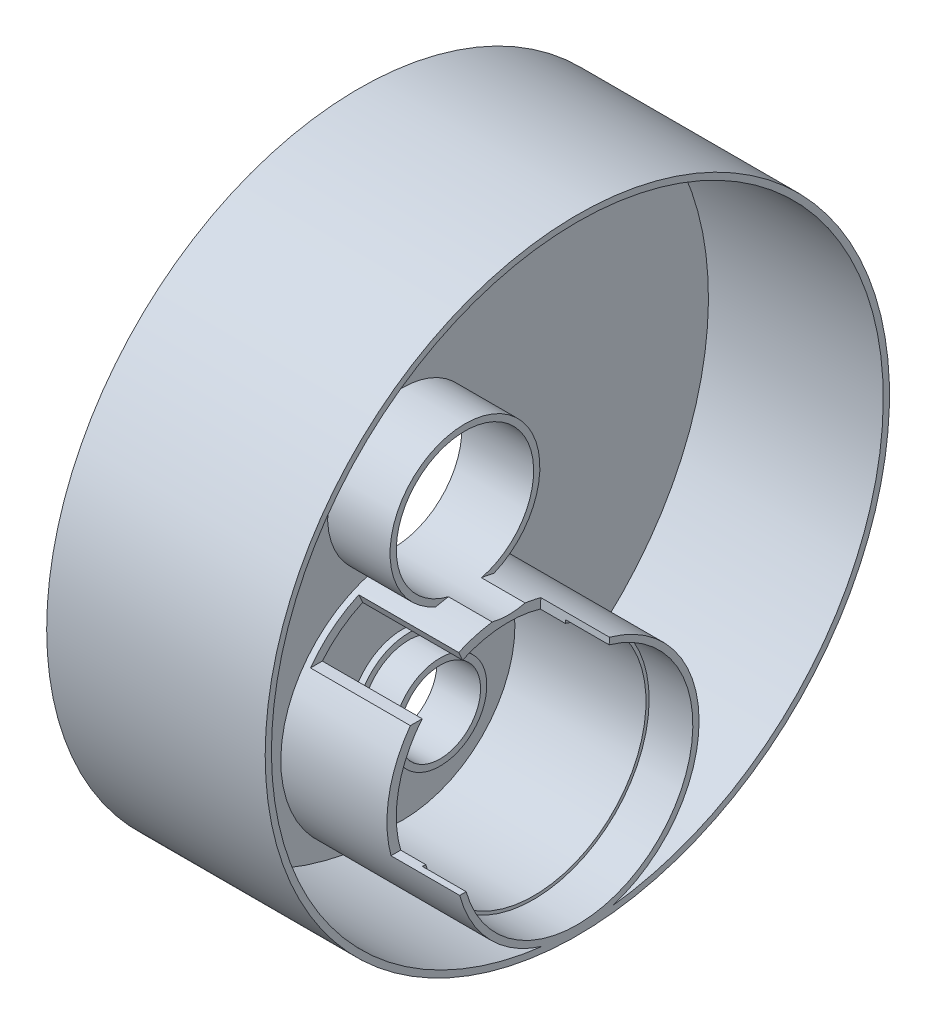
SolidWorks part; units mm, degrees
material "1060 Сплав"
ref_plane "Спереди" through (0, 0, 0) normal (0, 0, 1) x (1, 0, 0)
ref_plane "Сверху" through (0, 0, 0) normal (0, 1, 0) x (1, 0, 0)
ref_plane "Справа" through (0, 0, 0) normal (1, 0, 0) x (0, 0, -1)
sketch "Эскиз1" plane through (0, 0, 0) normal (0, 0, 1) x (1, 0, 0)
  line L0 (0, 0) -> (26039.5549, 0) construction
  line L1 (-27, 7.5) -> (-27, 8.5)
  line L2 (0, 19.5) -> (-29, 19.5)
  line L3 (-29, 19.5) -> (-29, 6.5)
  line L4 (-29, 6.5) -> (-22, 6.5)
  line L5 (-22, 6.5) -> (-22, 7.5)
  line L6 (-22, 7.5) -> (-27, 7.5)
  line L7 (-28, 8.5) -> (-28, 18)
  line L8 (-28, 18) -> (-7, 18)
  line L9 (-7, 18) -> (-7, 18.5)
  line L10 (-7, 18.5) -> (0, 18.5)
  line L11 (0, 18.5) -> (0, 19.5)
  line L12 (-27, 8.5) -> (-28, 8.5)
  dimension "D1" = 18.5
  dimension "D2" = 1
  dimension "D3" = 18
  dimension "D4" = 7
  dimension "D5" = 21
  dimension "D6" = 1
  dimension "D7" = 1
  dimension "D8" = 1
  dimension "D9" = 7.5
  dimension "D10" = 1
  dimension "D11" = 13
  dimension "D12" = 0.5
  dimension "D13" = 5
revolve "Повернуть1" add sketch "Эскиз1" angle 360 about L0
sketch "Эскиз2" plane through (0, 0, 0) normal (1, 0, 0) x (0, 0, -1)
  line L0 (0, 0) -> (0, 50000) construction
  line L1 (5.1563, 18.8059) -> (5, 16.2481)
  line L2 (5, 0) -> (5, 50000) construction
  line L3 (0, 0) -> (0, -5) construction
  line L4 (0, -5) -> (-50000, -5) construction
  line L5 (-18.8481, -5) -> (-16.2481, -5)
  line L6 (-5, 0) -> (-5, 50000) construction
  arc A0 (5, 16.2481) -> (-16.2481, -5) centre (0, 0) ccw
  arc A1 (-18.8481, -5) -> (5.1563, 18.8059) centre (0, 0) cw
  circle A2 centre (0, 0) radius 19.5 construction
  dimension "D3" = 17
  dimension "D4" = 19.5
  dimension "D1" = 5
  dimension "D2" = 5
  dimension "D5" = 2.5626
  dimension "D6" = 0
extrude "Вырез-Вытянуть1" cut sketch "Эскиз2" against normal blind 11 contours A0 L5 A1 L1
sketch "Эскиз3" plane through (0, 0, 0) normal (1, 0, 0) x (0, 0, -1)
  line L3 (-40, 11.5) -> (-12.52, 11.5)
  line L4 (0, 0) -> (-20535.6471, 45588.2353) construction
  line L5 (-6.9821, 15.5) -> (-13.2408, 29.394)
  line L6 (-13.2408, 29.394) -> (-40, 11.5)
  line L7 (0, 15.5) -> (-50000, 15.5) construction
  circle A0 centre (0, 0) radius 15.5 construction
  circle A1 centre (0, 0) radius 11.5 construction
  arc A2 (-6.9821, 15.5) -> (-12.52, 11.5) centre (0, 0) ccw
  dimension "D1" = 31
  dimension "D2" = 23
  dimension "D4" = 34
  dimension "D3" = 15.2386
  dimension "D5" = 32.1908
extrude "Вырез-Вытянуть2" cut sketch "Эскиз3" against normal blind 27
sketch "Эскиз4" plane through (-29, 0, 0) normal (-1, 0, 0) x (0, 0, 1)
  circle A1 centre (0, 30) radius 50
  circle A3 centre (0, 0) radius 6.5 construction
  circle A4 centre (0, 0) radius 6.5
  dimension "D2" = 100
  dimension "D5" = 13
  dimension "D1" = 30
  dimension "D4" = 30
extrude "Бобышка-Вытянуть1" add sketch "Эскиз4" against normal blind 1
sketch "Эскиз5" plane through (-29, 0, 0) normal (-1, 0, 0) x (0, 0, 1)
  circle A0 centre (0, 30) radius 50
  circle A1 centre (0, 30) radius 49
  dimension "D1" = 100
  dimension "D2" = 98
extrude "Бобышка-Вытянуть2" add sketch "Эскиз5" against normal blind 29 and the other way blind 6
sketch "Эскиз15" plane through (-28, 0, 0) normal (-1, 0, 0) x (0, 0, 1)
  circle A0 centre (0, 30) radius 11
  circle A1 centre (0, 30) radius 12
  dimension "D1" = 1
  dimension "D2" = 24
extrude "Бобышка-Вытянуть3" add sketch "Эскиз15" against normal blind 10 and the other way blind 1.5
sketch "Эскиз16" plane through (-28, 0, 0) normal (1, 0, 0) x (0, 0, -1)
  circle A0 centre (0, 30) radius 11
  arc A1 (2.6373, 19.3208) -> (-2.6373, 19.3208) centre (0, 30) ccw construction
extrude "Вырез-Вытянуть4" cut sketch "Эскиз16" against normal through all both and the other way through all
sketch "Эскиз12" plane through (-29, 0, 0) normal (-1, 0, 0) x (0, 0, 1)
  line L0 (0, 30) -> (0, 56.4) construction
  circle A0 centre (0, 56.4) radius 5
  dimension "D2" = 10
  dimension "D1" = 26.4
extrude "Вырез-Вытянуть3" cut sketch "Эскиз12" against normal up to next
hole_wizard "Сверление под метчик M2x0.41" positions "Эскиз13" profile "Эскиз14" hole size "M2x0.4" standard "Ansi Metric" end condition through all
sketch "Эскиз13" plane through (-29, 0, 0) normal (-1, 0, 0) x (0, 0, 1)
  line L0 (0, 56.4) -> (0, 62.9) construction
  point P0 (0, 62.9)
  dimension "D1" = 6.5
sketch "Эскиз14" plane through (-29, 62.9, 0) normal (0, 1, 0) x (0, 0, 1)
  line L0 (0, 0) -> (0, 29)
  line L1 (0, 29) -> (0.8, 29)
  line L2 (0.8, 29) -> (0.8, 0)
  line L5 (0.8, 0) -> (0, 0)
  line L11 (0, -6.35) -> (0, 107.95) construction
  dimension "Диаметр сквозного отверстия" = 1.6
  dimension "Глубина сквозного отверстия" = 29
pattern_circular "Круговой массив1" count 3 over 360 about axis through (0.001, 56.4, 0) along (-1, 0, 0) of "Сверление под метчик M2x0.41"
